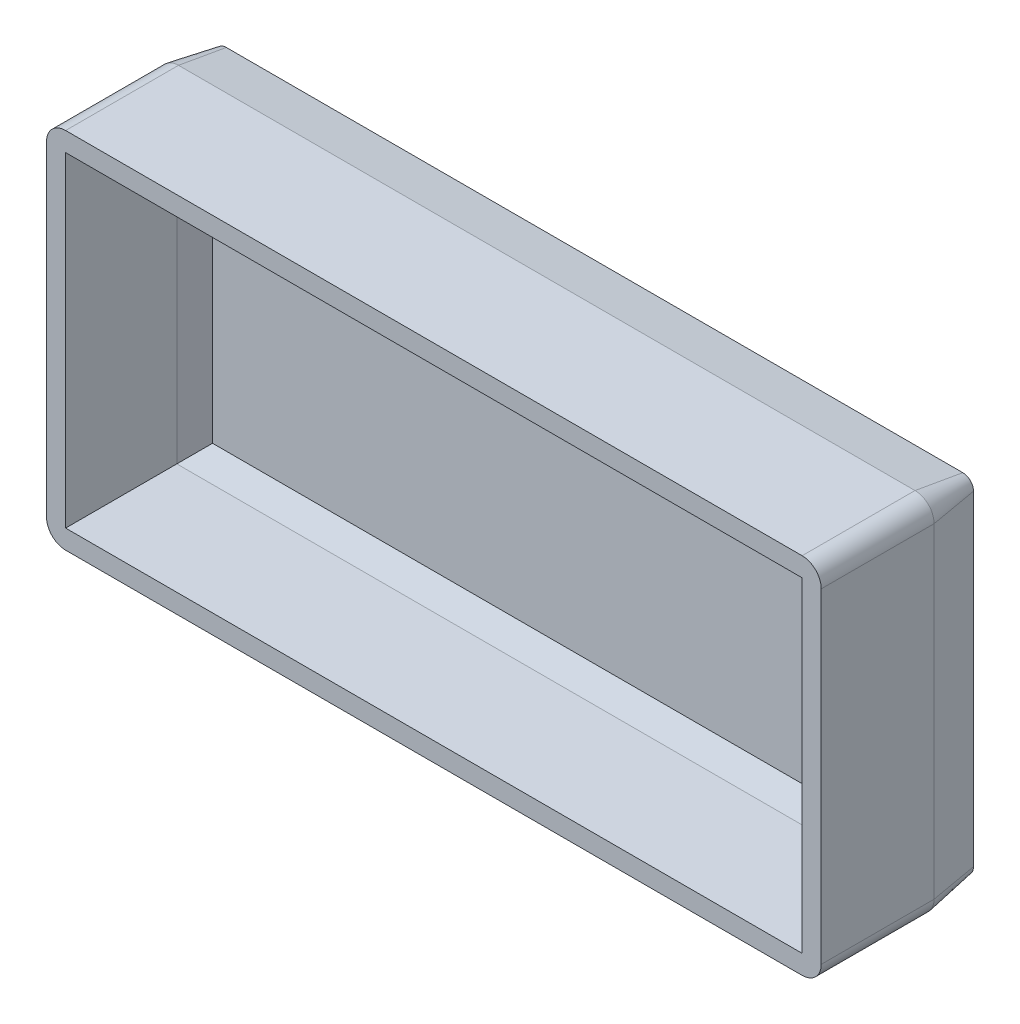
SolidWorks part; units mm, degrees
material "ABS"
ref_plane "Alzado" through (0, 0, 0) normal (0, 0, 1) x (1, 0, 0)
ref_plane "Planta" through (0, 0, 0) normal (0, 1, 0) x (1, 0, 0)
ref_plane "Vista lateral" through (0, 0, 0) normal (1, 0, 0) x (0, 0, -1)
sketch "Croquis1" plane through (0, 0, 0) normal (0, 0, 1) x (1, 0, 0)
  line L0 (-20.25, 8.5) -> (-20.25, -8.5)
  line L1 (-19.25, -9.5) -> (19.25, -9.5)
  line L2 (20.25, -8.5) -> (20.25, 8.5)
  line L3 (19.25, 9.5) -> (-19.25, 9.5)
  arc A0 (20.25, 8.5) -> (19.25, 9.5) centre (19.25, 8.5) ccw
  arc A1 (19.25, -9.5) -> (20.25, -8.5) centre (19.25, -8.5) ccw
  arc A2 (-20.25, 8.5) -> (-19.25, 9.5) centre (-19.25, 8.5) cw
  arc A3 (-20.25, -8.5) -> (-19.25, -9.5) centre (-19.25, -8.5) ccw
  point P4 (-20.25, 0)
  point P5 (0, -9.5)
  point P6 (20.25, 0)
  point P7 (0, 9.5)
  dimension "D1" = 1
  dimension "D2" = 19
  dimension "D3" = 40.5
extrude "Saliente-Extruir1" add sketch "Croquis1" along normal blind 5.9
extrude "Saliente-Extruir2" add sketch "Croquis1<2>" against normal blind 2.5 draft 10
sketch "Croquis1<2>" plane through (0, 0, 0) normal (0, 0, 1) x (1, 0, 0) same geometry as "Croquis1"
sketch "Croquis2" [suppressed]
  line L0 (-19.25, -6.25) -> (-21.5, -6.25)
  line L1 (-21.5, -6.25) -> (-21.5, -10.75)
  line L2 (-21.5, -10.75) -> (-17, -10.75)
  line L3 (-17, -10.75) -> (-17, -8.5)
  line L4 (19.25, -9.5) -> (-19.25, -9.5) construction
  line L5 (-20.25, -8.5) -> (-20.25, 8.5) construction
  arc A0 (-17, -8.5) -> (-19.25, -6.25) centre (-19.25, -8.5) ccw
  circle A1 centre (-18.65, -7.9) radius 0.8
  dimension "D1" = 4.5
  dimension "D2" = 1.6
  dimension "D3" = 1.6
  dimension "D4" = 1.6
sketch "Croquis2<2>" plane through (0, 0, -2.5) normal (0, 0, -1) x (-1, 0, 0) same geometry as "Croquis2"
shell "Vaciado1" thickness 1 removed face at (0, 0, 5.9)
sketch "Sketch1" plane through (0, 0, -2.5) normal (0, 0, -1) x (-1, 0, 0)
  circle A2 centre (10.95, 0) radius 3.5
extrude "Boss-Extrude1" add sketch "Sketch1" along normal blind 0.5
sketch "Sketch2" plane through (0, 0, -3) normal (0, 0, -1) x (-1, 0, 0)
  circle A0 centre (10.95, 0) radius 1.8 construction
  circle A1 centre (10.95, 0) radius 1.8
  arc A2 (9.6004, -2.2806) -> (9.7711, -2.3733) centre (10.95, 0) ccw construction
  arc A3 (9.6004, -2.2806) -> (9.7711, -2.3733) centre (10.95, 0) ccw construction
  circle A4 centre (10.95, 0) radius 2.65
extrude "Boss-Extrude2" add sketch "Sketch2" along normal blind 4
sketch "Sketch3" plane through (0, 0, -2.5) normal (0, 0, -1) x (-1, 0, 0)
  line L0 (19.25, -9.0592) -> (-19.25, -9.0592) construction
  line L1 (-19.8092, -8.5) -> (-19.8092, 8.5) construction
  line L2 (0, 0) -> (-19.8092, 0) construction
  circle A0 centre (-18.3092, -7.5592) radius 0.55
  circle A1 centre (-18.3092, 7.5592) radius 0.55
  point P9 (-19.8092, 0)
  dimension "D1" = 1.1
  dimension "D2" = 1.5
  dimension "D3" = 1.5
extrude "Cut-Extrude1" cut sketch "Sketch3" against normal blind 10
